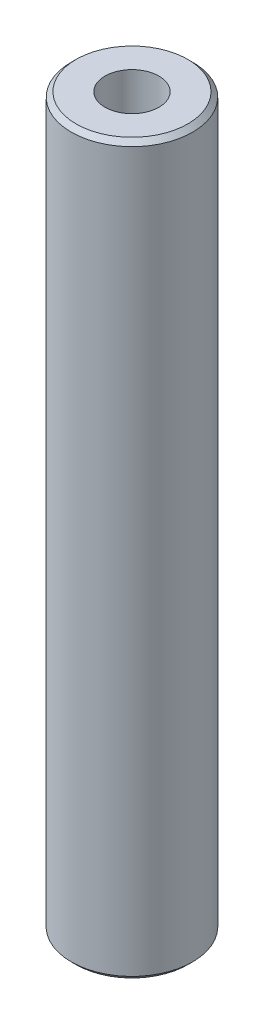
SolidWorks part; units mm, degrees
ref_plane "Front Plane" through (0, 0, 0) normal (0, 0, 1) x (1, 0, 0)
ref_plane "Top Plane" through (0, 0, 0) normal (0, 1, 0) x (1, 0, 0)
ref_plane "Right Plane" through (0, 0, 0) normal (1, 0, 0) x (0, 0, -1)
sketch "Sketch1" plane through (0, 0, 0) normal (0, 1, 0) x (1, 0, 0)
  circle A0 centre (0, 0) radius 50
  dimension "SHAFT_OD" = 100
extrude "Boss-Extrude1" add sketch "Sketch1" along normal blind 600
sketch "Sketch2" plane through (0, 0, 0) normal (0, 1, 0) x (1, 0, 0)
  circle A0 centre (0, 0) radius 22.2616
  dimension "BORE_D" = 44.5232
extrude "Cut-Extrude1" cut sketch "Sketch2" along normal through all
chamfer "Chamfer1" distance 3.9342 angle 45 2 edges at (0, 600, 50) (0, 0, 50)
